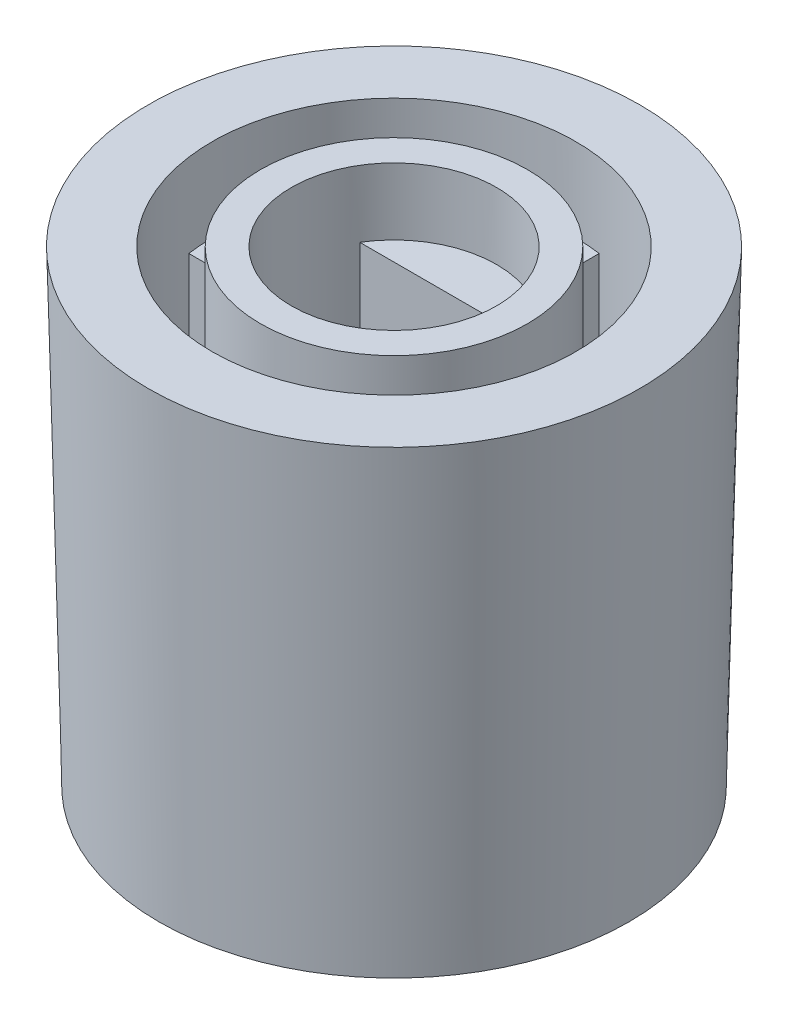
SolidWorks part; units mm, degrees
ref_plane "Front Plane" through (0, 0, 0) normal (0, 0, 1) x (1, 0, 0)
ref_plane "Top Plane" through (0, 0, 0) normal (0, 1, 0) x (1, 0, 0)
ref_plane "Right Plane" through (0, 0, 0) normal (1, 0, 0) x (0, 0, -1)
sketch "Sketch1" plane through (0, 0, 0) normal (0, 1, 0) x (1, 0, 0)
  circle A0 centre (0, 0) radius 7.04
  dimension "D1" = 14.08
extrude "Boss-Extrude1" add sketch "Sketch1" along normal blind 3.5
sketch "Sketch2" plane through (0, 3.5, 0) normal (0, 1, 0) x (1, 0, 0)
  circle A0 centre (0, 0) radius 7.04
  circle A1 centre (0, 0) radius 5.45
  circle A2 centre (0, 0) radius 7.04 construction
  dimension "D2" = 10.9
extrude "Boss-Extrude2" add sketch "Sketch2" along normal blind 10.5
draft "Draft1" type of draft neutral plane draft angle 1.325 faces to draft 1 face at (0, 0, 7.04) neutral plane through (0, 0, 0) neutral plane normal (0, -1, 0) parameters "D1"=1.325
sketch "Sketch6" plane through (0, 3.5, 0) normal (0, 1, 0) x (1, 0, 0)
  circle A0 centre (0, 0) radius 4
  dimension "D1" = 8
extrude "Boss-Extrude3" add sketch "Sketch6" along normal blind 10.5
sketch "Sketch5" plane through (0, 14, 0) normal (0, 1, 0) x (1, 0, 0)
  line L0 (-2.626, 1.6) -> (2.626, 1.6)
  circle A0 centre (0, 0) radius 3.075
  dimension "D1" = 6.15
  dimension "D2" = 1.6
extrude "Cut-Extrude1" cut sketch "Sketch5" against normal blind 9 contours L0 A0 region at (0, 14, 0.4982)
sketch "Sketch7" plane through (0, 14, 0) normal (0, 1, 0) x (1, 0, 0)
  circle A0 centre (0, 0) radius 3.075
  dimension "D1" = 6.15
extrude "Cut-Extrude2" cut sketch "Sketch7" against normal blind 2
sketch "Sketch8" plane through (0, 3.5, 0) normal (0, 1, 0) x (1, 0, 0)
  line L1 (-6.116, 0.75) -> (-3.5908, 0.75)
  line L2 (-6.116, 0.75) -> (-6.116, -0.75)
  line L3 (-6.116, -0.75) -> (-3.5908, -0.75)
  line L4 (-3.5908, 0.75) -> (-3.5908, -0.75)
  line L5 (3.6356, 0.75) -> (5.7578, 0.75)
  line L6 (3.6356, 0.75) -> (3.6356, -0.75)
  line L7 (3.6356, -0.75) -> (5.7578, -0.75)
  line L8 (5.7578, 0.75) -> (5.7578, -0.75)
  line L9 (-0.75, 3.5774) -> (0.75, 3.5774)
  line L10 (-0.75, 3.5774) -> (-0.75, 5.9145)
  line L11 (-0.75, 5.9145) -> (0.75, 5.9145)
  line L12 (0.75, 3.5774) -> (0.75, 5.9145)
  line L13 (0.75, -3.4431) -> (-0.75, -3.4431)
  line L14 (0.75, -3.4431) -> (0.75, -6.2011)
  line L15 (0.75, -6.2011) -> (-0.75, -6.2011)
  line L16 (-0.75, -3.4431) -> (-0.75, -6.2011)
  point P16 (-3.5908, 0)
  point P18 (0, 3.5774)
  dimension "D1" = 1.5
extrude "Boss-Extrude4" add sketch "Sketch8" along normal blind 8
